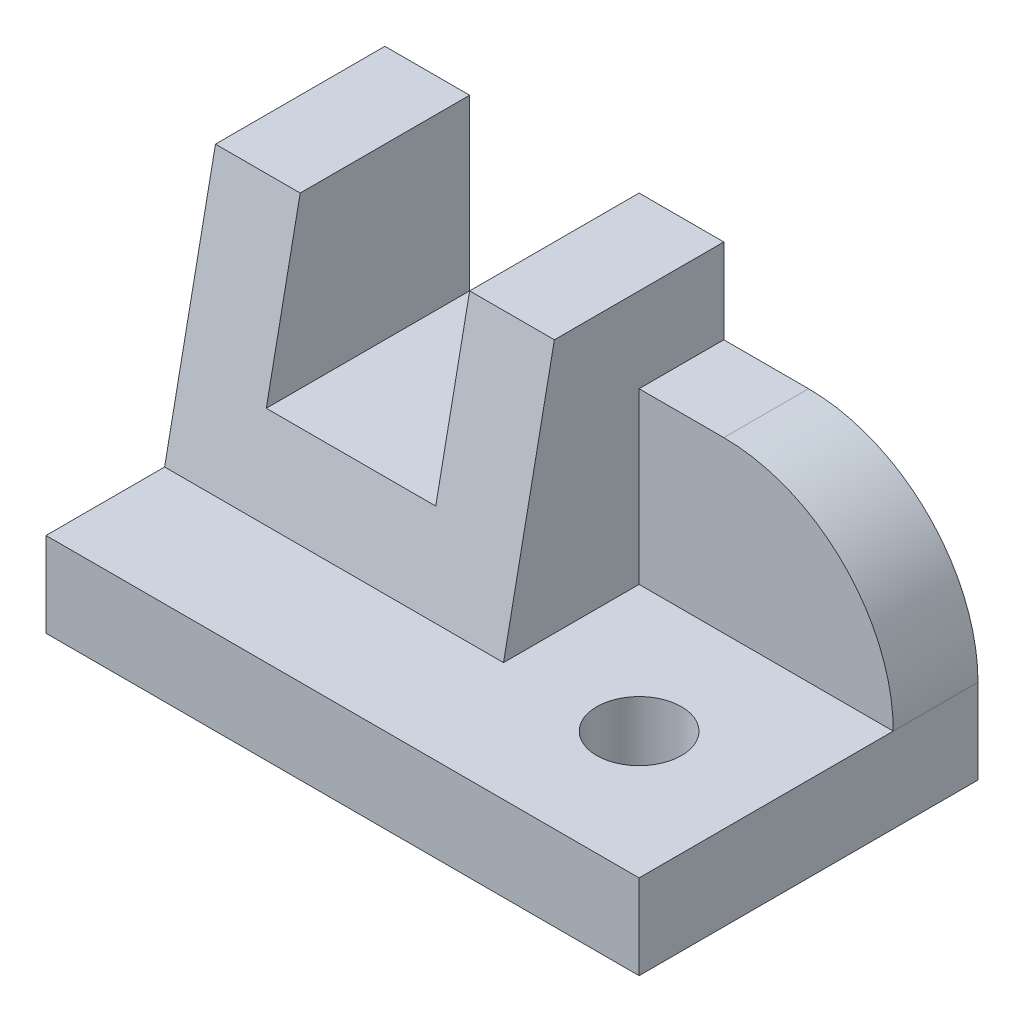
SolidWorks part; units mm, degrees
ref_plane "Front Plane" through (0, 0, 0) normal (0, 0, 1) x (1, 0, 0)
ref_plane "Top Plane" through (0, 0, 0) normal (0, 1, 0) x (1, 0, 0)
ref_plane "Right Plane" through (0, 0, 0) normal (1, 0, 0) x (0, 0, -1)
ref_plane "Plane1" through (0, 0, 0) normal (-1, 0, 0) x (0, -1, 0)
sketch "Sketch1" plane through (0, 0, 0) normal (-1, 0, 0) x (0, -1, 0)
  line L0 (-10, -14) -> (-40, -20)
  line L1 (-40, -20) -> (-10, -20)
  line L2 (-10, -20) -> (-10, -14)
  dimension "D1" = 30
  dimension "Width" = 6
extrude "Boss-Extrude1" add sketch "Sketch1" against normal blind 40
sketch "Sketch2" plane through (0, 0, -20) normal (0, 0, -1) x (-1, 0, 0)
  line L0 (-40, 40) -> (0, 40)
  line L1 (0, 40) -> (0, 10)
  line L2 (0, 10) -> (-40, 10)
  line L3 (-40, 10) -> (-40, 40)
extrude "Boss-Extrude2" add sketch "Sketch2" along normal blind 20
sketch "Sketch3" plane through (40, 0, 0) normal (1, 0, 0) x (0, 0, -1)
  line L0 (40, 10) -> (0, 10)
  line L1 (0, 10) -> (20, 40)
  line L2 (20, 40) -> (40, 40)
  line L3 (40, 40) -> (40, 10)
extrude "Boss-Extrude3" add sketch "Sketch3" along normal blind 30
sketch "Sketch4" plane through (70, 0, 0) normal (1, 0, 0) x (0, 0, -1)
  line L0 (20, 40) -> (0, 10)
  line L1 (0, 10) -> (30, 10)
  line L2 (30, 10) -> (30, 30)
  line L3 (30, 30) -> (40, 30)
  line L4 (40, 30) -> (40, 40)
  line L5 (40, 40) -> (20, 40)
extrude "Cut-Extrude1" cut sketch "Sketch4" against normal blind 30
sketch "Sketch5" plane through (0, 10, 0) normal (0, -1, 0) x (1, 0, 0)
  line L0 (70, 0) -> (70, -40)
  line L1 (70, -40) -> (0, -40)
  line L2 (0, -40) -> (0, 0)
  line L3 (0, 0) -> (70, 0)
extrude "Boss-Extrude4" add sketch "Sketch5" along normal blind 10
sketch "Sketch6" plane through (0, 0, -40) normal (0, 0, -1) x (-1, 0, 0)
  line L0 (-30, 40) -> (-30, 20)
  line L1 (-30, 20) -> (-10, 20)
  line L2 (-10, 20) -> (-10, 40)
  line L3 (-10, 40) -> (-30, 40)
extrude "Cut-Extrude2" cut sketch "Sketch6" against normal through all
hole_wizard "Ø10.0 (10) Diameter Hole1" positions "Sketch8" profile "Sketch7" hole size "Ø10.0" standard "ANSI Metric"
sketch "Sketch8" plane through (0, 0, 0) normal (0, -1, 0) x (-1, 0, 0)
  point P0 (-55, 15)
sketch "Sketch7" plane through (55, 0, -15) normal (1, 0, 0) x (0, 0, -1)
  line L0 (0, 0) -> (0, 40)
  line L1 (0, 40) -> (5, 40)
  line L2 (5, 40) -> (5, 0)
  line L5 (5, 0) -> (0, 0)
  line L11 (0, -6.35) -> (0, 107.95) construction
  dimension "Thru Hole Dia." = 10
  dimension "Thru Hole Depth" = 40
fillet "Fillet1" radius 20 1 edges at (70, 30, -35) tangent propagation no
